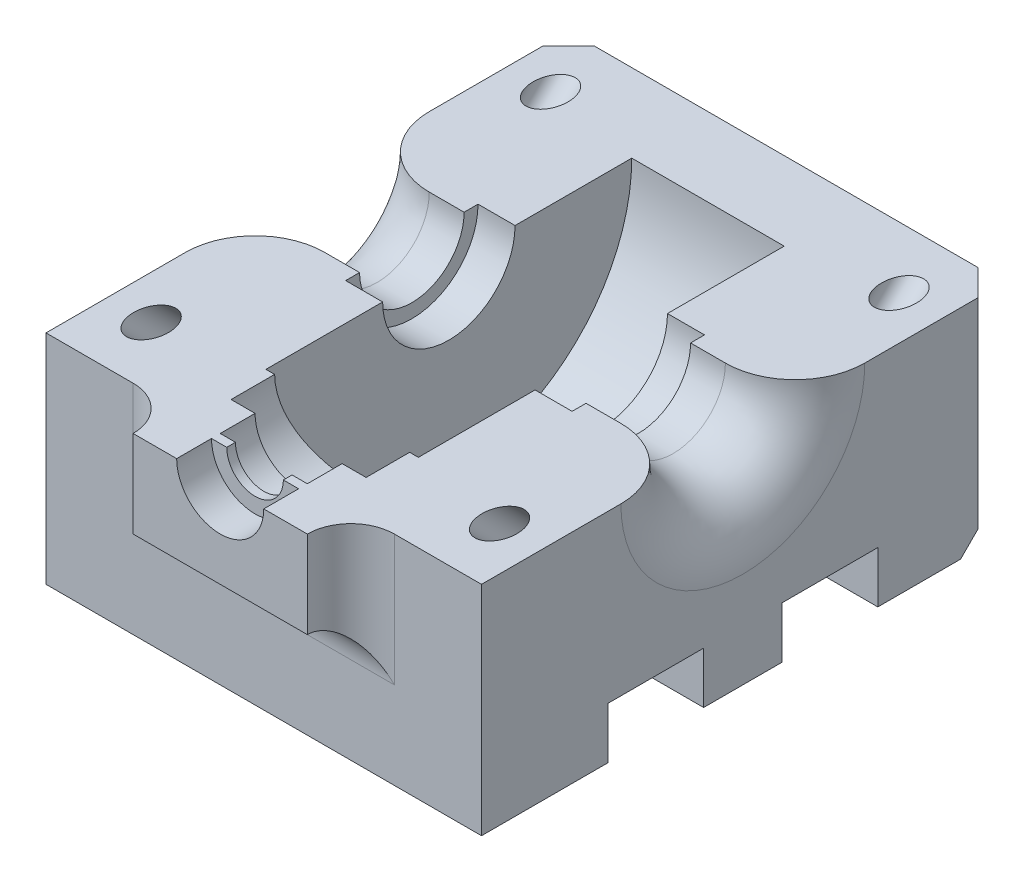
SolidWorks part; units mm, degrees
ref_plane "Front Plane" through (0, 0, 0) normal (0, 0, 1) x (1, 0, 0)
ref_plane "Top Plane" through (0, 0, 0) normal (0, 1, 0) x (1, 0, 0)
ref_plane "Right Plane" through (0, 0, 0) normal (1, 0, 0) x (0, 0, -1)
sketch "Sketch1" plane through (0, 0, 0) normal (0, 1, 0) x (1, 0, 0)
  line L1 (-25, 30) -> (25, 30)
  line L2 (-25, 30) -> (-25, -30)
  line L3 (-25, -30) -> (25, -30)
  line L4 (25, 30) -> (25, -30)
  line L5 (-25, 30) -> (25, -30) construction
  line L6 (-25, -30) -> (25, 30) construction
  point P0 (0, 0)
  dimension "D1" = 50
  dimension "D2" = 60
extrude "Boss-Extrude1" add sketch "Sketch1" along normal blind 25
sketch "Sketch2" plane through (-25, 0, 0) normal (-1, 0, 0) x (0, 0, 1)
  line L3 (-30, 25) -> (30, 25) construction
  line L6 (-30, 25) -> (-30, 0) construction
  circle A1 centre (0, 25) radius 21
  dimension "D1" = 42
  dimension "D2" = 9
extrude "Cut-Extrude1" cut sketch "Sketch2" against normal blind 17.5 from offset 16.25 offset against normal yes
sketch "Sketch3" plane through (-25, 0, 0) normal (-1, 0, 0) x (0, 0, 1)
  line L0 (-30, 25) -> (30, 25) construction
  line L1 (30, 25) -> (30, 0) construction
  circle A0 centre (0, 25) radius 7.6
  dimension "D1" = 15.2
  dimension "D2" = 30
extrude "Cut-Extrude2" cut sketch "Sketch3" against normal blind 26 from offset 12 offset against normal yes
sketch "Sketch4" plane through (0, 0, 30) normal (0, 0, 1) x (1, 0, 0)
  line L0 (-25, 25) -> (25, 25) construction
  circle A0 centre (0, 25) radius 5
  dimension "D1" = 10
extrude "Cut-Extrude3" cut sketch "Sketch4" against normal blind 4
sketch "Sketch5" plane through (0, 0, 0) normal (0, -1, 0) x (1, 0, 0)
  line L0 (-25, -30) -> (-25, 30) construction
  line L1 (25, -30) -> (-25, -30) construction
  circle A0 centre (-10, 20) radius 1.75
  circle A1 centre (10, 20) radius 1.75
  circle A2 centre (-10, -20) radius 1.75
  circle A3 centre (10, -20) radius 1.75
  dimension "D1" = 3.5
  dimension "D2" = 3.5
  dimension "D3" = 3.5
  dimension "D4" = 3.5
  dimension "D5" = 20
  dimension "D6" = 15
  dimension "D7" = 20
  dimension "D8" = 15
  dimension "D9" = 40
  dimension "D10" = 40
  dimension "D11" = 10
  dimension "D12" = 10
extrude "Cut-Extrude4" cut sketch "Sketch5" against normal blind 10
chamfer "Chamfer1" distance 5 angle 45 1 edges at (0, 0, -30)
sketch "Sketch6" plane through (0, 0, -30) normal (0, 0, -1) x (-1, 0, 0)
  line L0 (25, 25) -> (25, 5) construction
  line L1 (25, 0) -> (-25, 0) construction
  circle A0 centre (-20, 15) radius 2
  circle A1 centre (20, 15) radius 2
  dimension "D1" = 4
  dimension "D2" = 4
  dimension "D3" = 40
  dimension "D4" = 5
  dimension "D5" = 15
  dimension "D6" = 15
extrude "Cut-Extrude5" cut sketch "Sketch6" against normal blind 10
sketch "Sketch7" plane through (25, 0, 0) normal (1, 0, 0) x (0, 0, -1)
  line L0 (-30, 0) -> (25, 0) construction
  line L1 (-4.5, 0) -> (-15.5, 0)
  line L2 (-4.5, 0) -> (-4.5, 5.9067)
  line L3 (-4.5, 5.9067) -> (-15.5, 5.9067)
  line L4 (-15.5, 0) -> (-15.5, 5.9067)
  line L5 (30, 25) -> (30, 5) construction
  line L6 (15.5, 0) -> (4.5, 0)
  line L7 (15.5, 0) -> (15.5, 5.9067)
  line L8 (15.5, 5.9067) -> (4.5, 5.9067)
  line L9 (4.5, 0) -> (4.5, 5.9067)
  dimension "D1" = 14.5
  dimension "D2" = 11
  dimension "D3" = 9
  dimension "D4" = 11
extrude "Cut-Extrude6" cut sketch "Sketch7" against normal blind 9
chamfer "Chamfer2" distance 5 angle 45 2 edges at (16, 5.9067, -10) (16, 5.9067, 10)
mirror "Mirror1" about plane through (0, 0, 0) normal (1, 0, 0) of "Chamfer2", "Cut-Extrude6"
chamfer "Chamfer3" distance 3 angle 45 2 edges at (25, 15, -30) (-25, 15, -30)
ref_plane "Plane1" through (0, -2.5, -2.5) normal (0, 0.7071, 0.7071) x (1, 0, 0)
sketch "Sketch10" plane through (0, -2.5, -2.5) normal (0, 0.7071, 0.7071) x (1, 0, 0)
  line L0 (-25, 36.7696) -> (-25, -3.5355) construction
  line L1 (-25, -3.5355) -> (-5, -3.5355) construction
  circle A0 centre (-20, 1.4645) radius 2
  circle A1 centre (20, 1.4645) radius 2
  dimension "D1" = 4
  dimension "D3" = 4
  dimension "D2" = 40
  dimension "D4" = 5
  dimension "D5" = 5
extrude "Cut-Extrude8" cut sketch "Sketch10" along normal through all from offset 25
mirror "Mirror2" about plane through (0, 0, 0) normal (0, 0, 1) of "Cut-Extrude8"
sketch "Sketch12" plane through (-25, 0, 0) normal (-1, 0, 0) x (0, 0, 1)
  circle A0 centre (0, 25) radius 6
  dimension "D1" = 12
extrude "Cut-Extrude10" cut sketch "Sketch12" against normal through all both and the other way through all
fillet "Fillet1" radius 8 2 edges at (25, 19, 0)
sketch "Sketch16" plane through (0, 0, 26) normal (0, 0, 1) x (1, 0, 0)
  line L0 (8.75, 25) -> (-8.75, 25) construction
  circle A0 centre (0, 25) radius 7.75
  dimension "D1" = 15.5
extrude "Cut-Extrude13" cut sketch "Sketch16" against normal blind 8
sketch "Sketch17" plane through (0, 0, 30) normal (0, 0, 1) x (1, 0, 0)
  line L0 (-25, 25) -> (-5, 25) construction
  line L1 (-10, 25) -> (10, 25)
  line L2 (-10, 25) -> (-10, 15)
  line L3 (-10, 15) -> (10, 15)
  line L4 (10, 25) -> (10, 15)
  dimension "D1" = 5
  dimension "D2" = 5
  dimension "D3" = 10
extrude "Boss-Extrude2" add sketch "Sketch17" along normal blind 5
sketch "Sketch18" plane through (0, 0, 30) normal (0, 0, -1) x (-1, 0, 0)
  line L0 (-22, 25) -> (22, 25) construction
  circle A0 centre (0, 25) radius 3.25
  dimension "D1" = 6.5
extrude "Cut-Extrude14" cut sketch "Sketch18" against normal blind 10
sketch "Sketch19" plane through (0, 0, 35) normal (0, 0, 1) x (1, 0, 0)
  line L0 (8.75, 25) -> (-8.75, 25) construction
  circle A0 centre (0, 25) radius 5
  dimension "D1" = 10
extrude "Cut-Extrude15" cut sketch "Sketch19" against normal blind 4
fillet "Fillet2" radius 5 3 edges at (-10, 20, 30) (0, 15, 30) (10, 20, 30)
